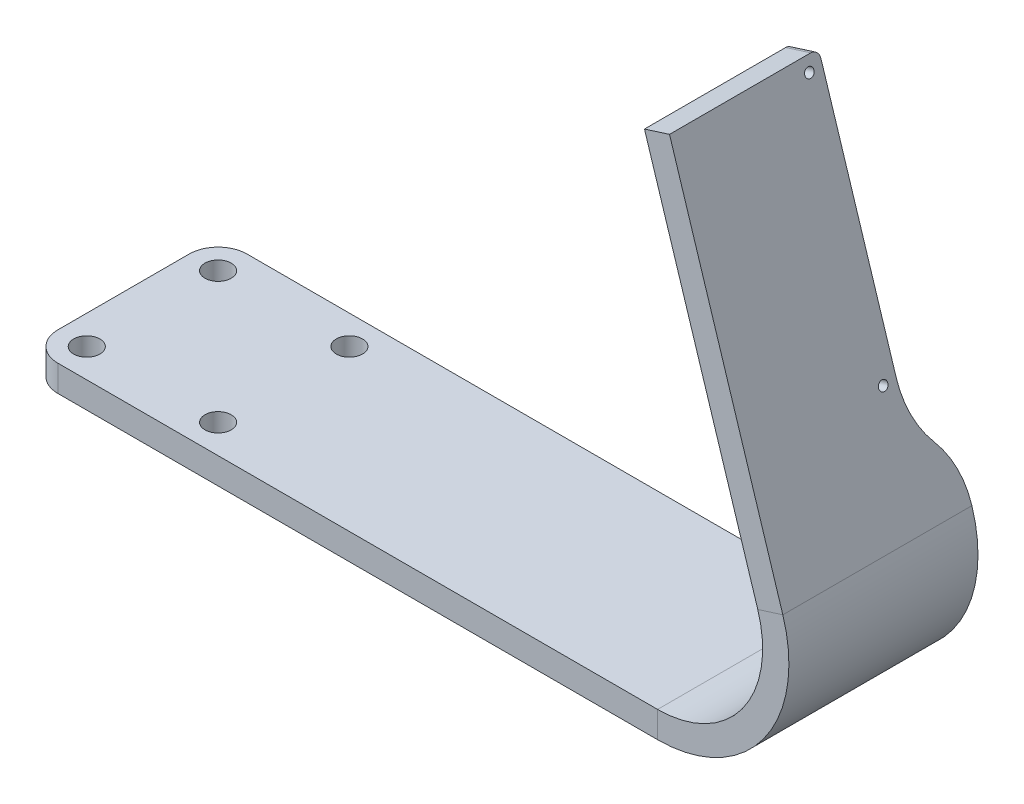
SolidWorks part; units mm, degrees
ref_plane "Front" through (0, 0, 0) normal (0, 0, 1) x (1, 0, 0)
ref_plane "Top" through (0, 0, 0) normal (0, 1, 0) x (1, 0, 0)
ref_plane "Right" through (0, 0, 0) normal (1, 0, 0) x (0, 0, -1)
sketch "Sketch2" plane through (0, 0, 0) normal (0, 1, 0) x (1, 0, 0)
  line L0 (-18, -12.5) -> (-18, 12.5)
  line L1 (-12.5, -12.5) -> (12.5, -12.5) construction
  line L2 (-12.5, -12.5) -> (-12.5, 12.5) construction
  line L3 (-12.5, 12.5) -> (12.5, 12.5) construction
  line L4 (12.5, -12.5) -> (12.5, 12.5) construction
  line L5 (-12.5, -12.5) -> (12.5, 12.5) construction
  line L6 (-12.5, 12.5) -> (12.5, -12.5) construction
  line L7 (-12.5, -18) -> (12.5, -18)
  line L8 (18, -12.5) -> (18, 12.5)
  line L9 (-12.5, 18) -> (12.5, 18)
  line L10 (12.5, 18) -> (18, 18)
  line L11 (18, 18) -> (18, 12.5)
  line L12 (12.5, -18) -> (18, -18)
  line L13 (18, -18) -> (18, -12.5)
  arc A0 (-18, 12.5) -> (-12.5, 18) centre (-12.5, 12.5) cw
  arc A1 (18, 12.5) -> (12.5, 18) centre (12.5, 12.5) ccw construction
  arc A2 (18, -12.5) -> (12.5, -18) centre (12.5, -12.5) cw construction
  arc A3 (-12.5, -18) -> (-18, -12.5) centre (-12.5, -12.5) cw
  circle A4 centre (-12.5, 12.5) radius 2.5
  circle A5 centre (12.5, 12.5) radius 2.5
  circle A6 centre (12.5, -12.5) radius 2.5
  circle A7 centre (-12.5, -12.5) radius 2.5
  point P0 (0, 0)
  dimension "D1" = 5
  dimension "D2" = 3
  dimension "D3" = 25
extrude "Boss-Extrude1" add sketch "Sketch2" along normal mid plane 5
sketch "Sketch5" plane through (18, 0, 0) normal (1, 0, 0) x (0, 0, -1)
  line L4 (-18, -2.5) -> (18, -2.5)
  line L5 (18, -2.5) -> (18, 2.5)
  line L6 (18, 2.5) -> (-18, 2.5)
  line L7 (-18, 2.5) -> (-18, -2.5)
  line L8 (-18, -2.5) -> (18, -2.5)
  line L9 (18, -2.5) -> (18, 2.5)
  line L10 (18, 2.5) -> (-18, 2.5)
  line L11 (-18, 2.5) -> (-18, -2.5)
  dimension "D1" = 0
sketch "Sketch4" plane through (0, 0, 0) normal (0, 0, 1) x (1, 0, 0)
  line L0 (18, -2.5) -> (101.6747, -2.5)
  line L1 (125.5176, 30.0176) -> (118, 53.8606)
  arc A0 (101.6747, -2.5) -> (125.5176, 30.0176) centre (101.6747, 22.5) ccw
  dimension "D1" = 25
  dimension "D2" = 25
  dimension "D3" = 100
  dimension "D4" = 72.5
sweep "Sweep2" add profiles "Sketch5" path "Sketch4"
sketch "Sketch11" plane through (118.008, 37.2078, 0) normal (-0.9537, -0.3007, 0) x (0, 0, 1)
  line L0 (-33.75, 10.8845) -> (18, 10.8845)
  line L1 (-28.75, 15.8845) -> (13, 15.8845)
  line L2 (-28.75, 15.8845) -> (-28.75, 57.6345)
  line L3 (-28.75, 57.6345) -> (13, 57.6345)
  line L4 (13, 15.8845) -> (13, 57.6345)
  line L5 (18, 10.8845) -> (18, 62.6345)
  line L6 (-33.75, 62.6345) -> (18, 62.6345)
  line L7 (-33.75, 10.8845) -> (-33.75, 62.6345)
  line L8 (18, -9.1155) -> (18, 15.8845) construction
  line L9 (-18, 15.8845) -> (18, 15.8845) construction
  dimension "D2" = 41.75
  dimension "D1" = 5
extrude "Boss-Extrude2" add sketch "Sketch11" against normal up to surface (5 mm away) up to face at (121.7588, 41.9391, 0)
sketch "Sketch14" plane through (122.7765, 38.7113, 0) normal (0.9537, 0.3007, 0) x (0, 0, -1)
  line L0 (-13, 15.8845) -> (28.75, 15.8845) construction
  line L1 (28.75, 57.6345) -> (28.75, 15.8845) construction
  line L2 (-13, 57.6345) -> (28.75, 57.6345) construction
  line L3 (-13, 15.8845) -> (-13, 57.6345) construction
  line L4 (-13, 15.8845) -> (28.75, 15.8845)
  line L5 (28.75, 57.6345) -> (28.75, 15.8845)
  line L6 (-13, 57.6345) -> (28.75, 57.6345)
  line L7 (-13, 15.8845) -> (-13, 57.6345)
extrude "Boss-Extrude3" add sketch "Sketch14" against normal offset from surface (1.5 mm away) 3.5
fillet "Fillet1" radius 8 1 edges at (117.1192, 48.3402, -18)
sketch "Sketch18" plane through (118.008, 37.2078, 0) normal (-0.9537, -0.3007, 0) x (0, 0, 1)
  line L0 (-33.75, 10.8845) -> (18, 62.6345) construction
  line L1 (-7.875, 60.1345) -> (-7.875, 13.3845) construction
  line L2 (-28.75, 62.6345) -> (-28.75, 57.6345) construction
  line L3 (18, 62.6345) -> (-33.75, 62.6345) construction
  circle A0 centre (-7.875, 60.1345) radius 0.875
  circle A1 centre (-7.875, 13.3845) radius 0.875
  point P6 (-7.875, 36.7595)
  point P7 (-7.875, 36.7595)
  point P13 (-28.75, 60.1345)
  dimension "D1" = 1.75
extrude "Cut-Extrude3" cut sketch "Sketch18" against normal through all
sketch "Sketch19" plane through (121.346, 38.2602, 0) normal (-0.9537, -0.3007, 0) x (0, 0, 1)
  line L0 (-7.875, 60.1345) -> (-10.375, 62.6345) construction
  line L1 (18, 62.6345) -> (-33.75, 62.6345) construction
  line L2 (-10.375, 62.6345) -> (-10.375, 57.6345) construction
  line L3 (13, 57.6345) -> (-28.75, 57.6345) construction
  line L4 (-10.375, 57.6345) -> (-7.875, 60.1345) construction
  line L5 (-10.375, 62.6345) -> (-10.375, 13.3845)
  line L6 (-18, -9.1155) -> (-18, -29.1155) construction
  line L7 (-18, -9.1155) -> (-18, 2.8845) construction
  line L8 (-18, -9.1155) -> (18, -9.1155) construction
  line L9 (-18, -9.1155) -> (-33.75, -9.1155)
  line L10 (-33.75, -9.1155) -> (-33.75, 62.6345)
  line L11 (-33.75, 62.6345) -> (-10.375, 62.6345)
  arc A0 (-10.375, 13.3845) -> (-14.1875, 2.1345) centre (-28.8796, 13.3845) cw
  arc A1 (-18, -9.1155) -> (-14.1875, 2.1345) centre (0.5046, -9.1155) cw
  point P5 (-7.875, 13.3845)
extrude "Cut-Extrude4" cut sketch "Sketch19" against normal through all and the other way up to next
fillet "Fillet2" radius 1.5 3 edges at (114.9004, 52.8833, -10.375) (101.5577, 97.6951, -10.375) (102.346, 92.701, -10.375)
